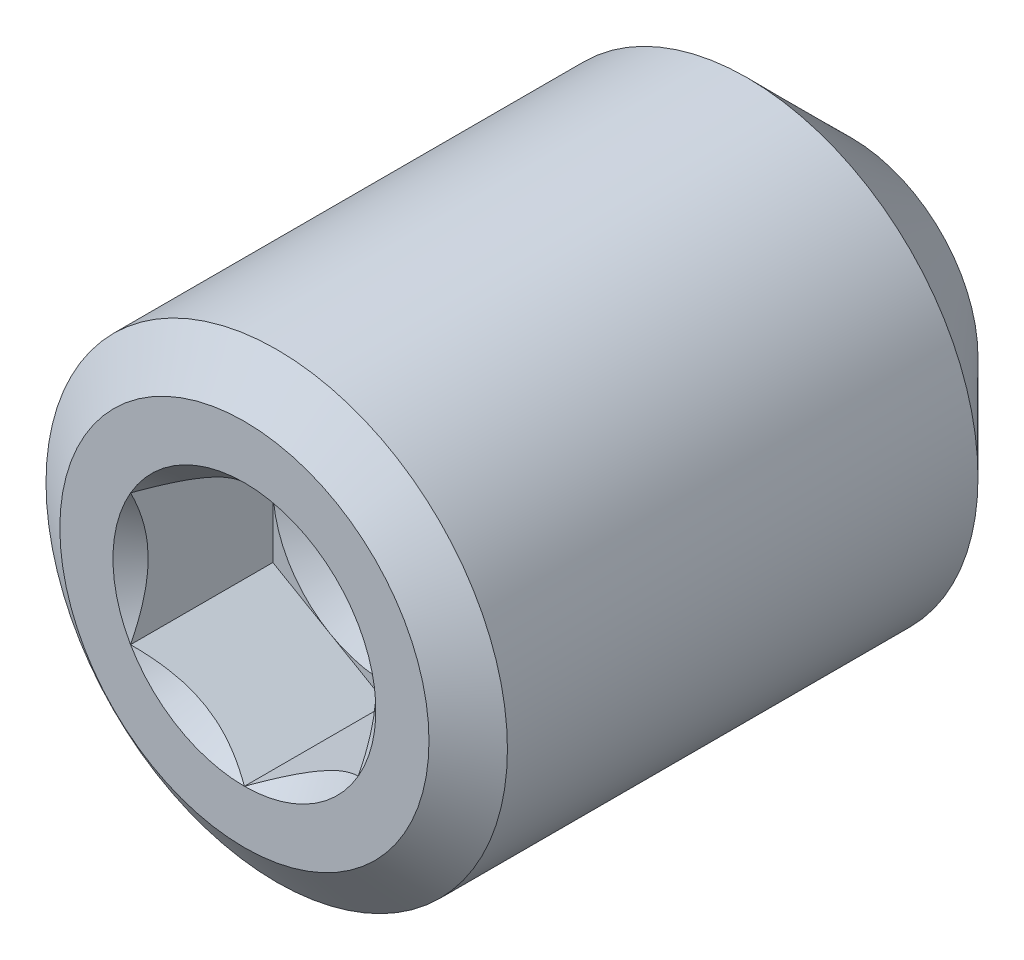
SolidWorks part; units mm, degrees
ref_plane "Front" through (0, 0, 0) normal (0, 0, 1) x (1, 0, 0)
ref_plane "Top" through (0, 0, 0) normal (0, 1, 0) x (1, 0, 0)
ref_plane "Right" through (0, 0, 0) normal (1, 0, 0) x (0, 0, -1)
sketch "Sketch22" plane through (0, 0, 0) normal (1, 0, 0) x (0, 0, -1)
  line L0 (-2.7778, 0) -> (-2.7778, 1.9304)
  line L1 (-2.7778, 1.9304) -> (-2.4398, 2.413)
  line L2 (-2.4398, 2.413) -> (2.4815, 2.413)
  line L3 (2.4815, 2.413) -> (3.5722, 1.3222)
  line L4 (3.5722, 1.3222) -> (2.7778, 0) construction
  line L5 (2.7778, 0) -> (-2.7778, 0)
  line L6 (2.7778, 0) -> (3.5722, 0) construction
  line L7 (3.5722, 0) -> (3.5722, 1.3222) construction
  line L8 (3.5722, -1.3222) -> (2.7778, 0) construction
  line L9 (-2.4398, -2.413) -> (2.4815, -2.413) construction
  line L10 (3.5722, 1.3222) -> (3.5722, 0)
  line L11 (3.5722, 0) -> (2.7778, 0)
  dimension "Dia" = 4.826
  dimension "Length" = 6.35
  dimension "D3" = 35
  dimension "D5" = 118
  dimension "D6" = 45
  dimension "D7" = 3.8608
revolve "Revolve1" add sketch "Sketch22" angle 360 about L6
ref_plane "Plane1" through (0, 0, -3.5722) normal (0, 0, 1) x (1, 0, 0)
sketch "Sketch27" plane through (0, 0, -3.5722) normal (0, 0, 1) x (1, 0, 0)
  circle A0 centre (0, 0) radius 2.413 construction
  circle A1 centre (0, 0) radius 2.413
curve "Helix/Spiral1" pitch 1.0583 height 7.4083 turns 7
sketch "Sketch28" plane through (0, 0, 0) normal (1, 0, 0) x (0, 0, -1)
  line L0 (3.5722, 2.413) -> (4.4983, 2.413)
  line L1 (4.4983, 2.413) -> (4.1014, 1.7256)
  line L2 (4.1014, 1.7256) -> (3.9691, 1.7256)
  line L3 (3.9691, 1.7256) -> (3.5722, 2.413)
  line L4 (3.7707, 2.0693) -> (4.2998, 2.0693) construction
  line L6 (-2.4398, 2.413) -> (2.4815, 2.413) construction
  line L7 (3.5722, 6.985) -> (3.5722, -6.985) construction
  dimension "D1" = 0.1323
  dimension "D3" = 60
  dimension "D2" = 0.5292
sweep "Cut-Sweep2" [suppressed] cut profiles "Sketch28" path "Helix/Spiral1"
sketch "Sketch23" plane through (0, 0, 2.7778) normal (0, 0, 1) x (1, 0, 0)
  line L1 (0, 1.3748) -> (-1.1906, 0.6874)
  line L2 (-1.1906, 0.6874) -> (-1.1906, -0.6874)
  line L3 (-1.1906, -0.6874) -> (0, -1.3748)
  line L4 (0, -1.3748) -> (1.1906, -0.6874)
  line L5 (1.1906, -0.6874) -> (1.1906, 0.6874)
  line L6 (1.1906, 0.6874) -> (0, 1.3748)
  circle A0 centre (0, 0) radius 1.1906 construction
  dimension "Hex" = 2.3813
extrude "Cut-Extrude10" cut sketch "Sketch23" against normal blind 1.4883
sketch "Sketch24" plane through (0, 0, 2.7778) normal (0, 0, 1) x (1, 0, 0)
  circle A0 centre (0, 0) radius 1.3748
extrude "Cut-Extrude11" cut sketch "Sketch24" against normal through all draft 45
sketch "Sketch26" plane through (0, 0, 1.2895) normal (0, 0, 1) x (1, 0, 0)
  circle A0 centre (0, 0) radius 1.1906 construction
  circle A1 centre (0, 0) radius 1.1906
extrude "Cut-Extrude12" cut sketch "Sketch26" against normal through all draft 60
sketch "Sketch30" plane through (0, 0, 0) normal (1, 0, 0) x (0, 0, -1)
  line L0 (-2.4398, 2.413) -> (2.4815, 2.413) construction
  line L1 (-2.7778, 0) -> (-2.7778, 1.9304) construction
  line L2 (3.5722, 0) -> (3.5722, 1.3222) construction
  line L3 (-2.4398, -2.413) -> (2.4815, -2.413) construction
  point P0 (-2.7778, 2.413)
  point P1 (3.5722, 2.413)
  point P2 (3.5722, -2.413)
  point P11 (-0.1319, -2.413)
  dimension "D1" = 3.7042
sketch "Sketch31" plane through (0, 0, 0) normal (1, 0, 0) x (0, 0, -1)
  line L2 (2.7778, 0) -> (3.5722, -1.3222)
  line L3 (3.5722, 1.3222) -> (2.7778, 0)
equation "\"D7@Sketch22\"=\"Dia@Sketch22\"*.8"
equation "\"D1@Sketch28\" = \"D4@Helix/Spiral1\" * .125"
equation "\"D3@Helix/Spiral1\" = \"Length@Sketch22\" + \"D4@Helix/Spiral1\""
equation "\"D1@Sketch30\" = \"D4@Helix/Spiral1\" * 3.5"
equation "\"hex Depth@Cut-Extrude10\" = \"Hex@Sketch23\" * .625"
equation "\"D2@Sketch28\" = \"D4@Helix/Spiral1\" * .5"
